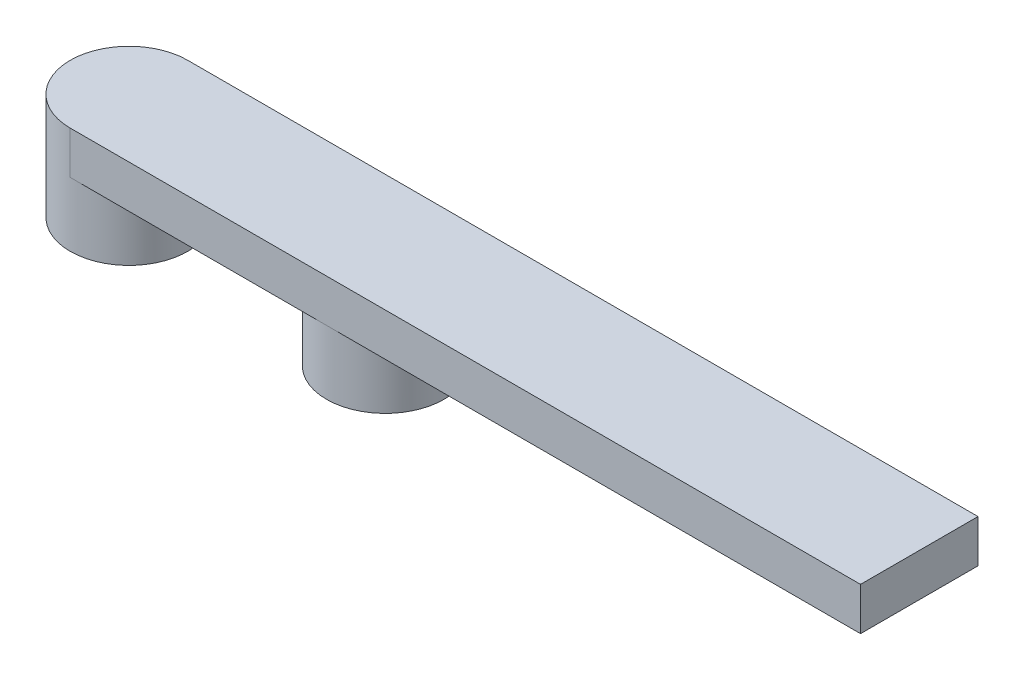
SolidWorks part; units mm, degrees
ref_plane "Front Plane" through (0, 0, 0) normal (0, 0, 1) x (1, 0, 0)
ref_plane "Top Plane" through (0, 0, 0) normal (0, 1, 0) x (1, 0, 0)
ref_plane "Right Plane" through (0, 0, 0) normal (1, 0, 0) x (0, 0, -1)
sketch "Sketch1" plane through (0, 0, 0) normal (0, 1, 0) x (1, 0, 0)
  line L0 (0, 0) -> (37, 0) construction
  line L1 (37, 2.75) -> (37, -2.75)
  line L2 (37, 2.75) -> (0, 2.75)
  line L4 (0, -2.75) -> (37, -2.75)
  circle A0 centre (0, 0) radius 2.75
  circle A1 centre (12, 0) radius 2.75
  arc A3 (0, 2.75) -> (0, -2.75) centre (0, 0) ccw
  point P10 (37, 0)
  dimension "D1" = 5.5
  dimension "D2" = 5.5
  dimension "D3" = 37
  dimension "D4" = 12
extrude "Boss-Extrude1" add sketch "Sketch1" along normal blind 2 contours A0 | A1 L0 | L0 A1 | A0 A1 L1 L2 A3 L4 | L2 A3 L4 L1 region at (25.5717, 0, -1.3947) region at (12, 0, 1.1671) region at (12, 0, -1.1671) region at (1.8895, 0, 1.8895)
extrude "Boss-Extrude2" add sketch "Sketch1<3>" against normal blind 3 contours A0 | L0 A1 | A1 L0 region at (12, 0, 1.1671) region at (12, 0, -1.1671) region at (1.8895, 0, 1.8895)
sketch "Sketch1<3>" plane through (0, 0, 0) normal (0, 1, 0) x (1, 0, 0) same geometry as "Sketch1"
sketch "Sketch2" plane through (0, 2, 0) normal (0, 1, 0) x (1, 0, 0)
  line L0 (14.8462, 0.9046) -> (35, 0.9046) construction
  text T0 "Stop" font "Century Gothic" height 2.5
extrude "Cut-Extrude1" [suppressed] cut sketch "Sketch2" against normal blind 1
